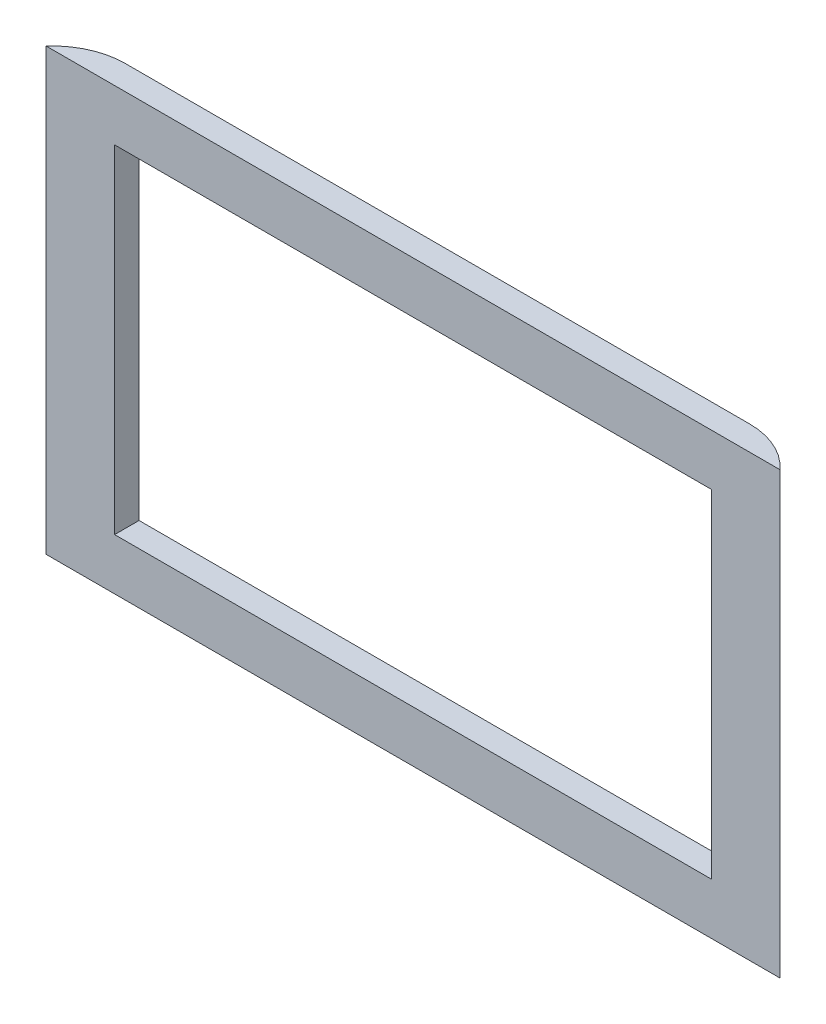
SolidWorks part; units mm, degrees
ref_plane "Front Plane" through (0, 0, 0) normal (0, 0, 1) x (1, 0, 0)
ref_plane "Top Plane" through (0, 0, 0) normal (0, 1, 0) x (1, 0, 0)
ref_plane "Right Plane" through (0, 0, 0) normal (1, 0, 0) x (0, 0, -1)
sketch "Sketch1" plane through (0, 0, 0) normal (0, 0, 1) x (1, 0, 0)
  line L1 (-75, 45) -> (75, 45)
  line L2 (-75, 45) -> (-75, -45)
  line L3 (-75, -45) -> (75, -45)
  line L4 (75, 45) -> (75, -45)
  line L5 (-75, 45) -> (75, -45) construction
  line L6 (-75, -45) -> (75, 45) construction
  line L7 (-61, 34.5) -> (61, 34.5)
  line L8 (-61, 34.5) -> (-61, -34.5)
  line L9 (-61, -34.5) -> (61, -34.5)
  line L10 (61, 34.5) -> (61, -34.5)
  line L11 (-61, 34.5) -> (61, -34.5) construction
  line L12 (-61, -34.5) -> (61, 34.5) construction
  point P0 (0, 0)
  point P6 (0, 0)
  dimension "D1" = 122
  dimension "D2" = 150
  dimension "D3" = 69
  dimension "D4" = 90
extrude "Boss-Extrude1" add sketch "Sketch1" along normal blind 5
fillet "Fillet2" radius 15 2 edges at (75, 0, 0) (-75, 0, 0)
